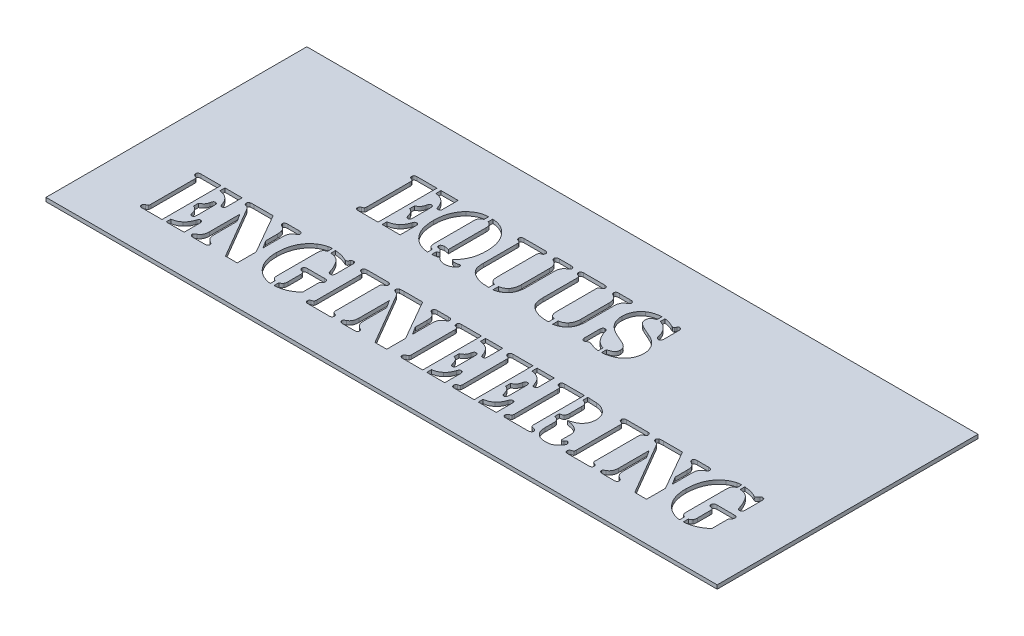
SolidWorks part; units mm, degrees
ref_plane "Front Plane" through (0, 0, 0) normal (0, 0, 1) x (1, 0, 0)
ref_plane "Top Plane" through (0, 0, 0) normal (0, 1, 0) x (1, 0, 0)
ref_plane "Right Plane" through (0, 0, 0) normal (1, 0, 0) x (0, 0, -1)
sketch "Sketch2" plane through (0, 0, 0) normal (0, 1, 0) x (1, 0, 0)
  line L1 (-43.3991, 100.4) -> (536.2046, 100.4)
  line L2 (-43.3991, 100.4) -> (-43.3991, -124.8346)
  line L3 (-43.3991, -124.8346) -> (536.2046, -124.8346)
  line L4 (536.2046, 100.4) -> (536.2046, -124.8346)
  text T0 "     EQUUS\r\nENGINEERING" font "Stencil" height 50.8
extrude "Boss-Extrude1" add sketch "Sketch2" along normal blind 3.302
